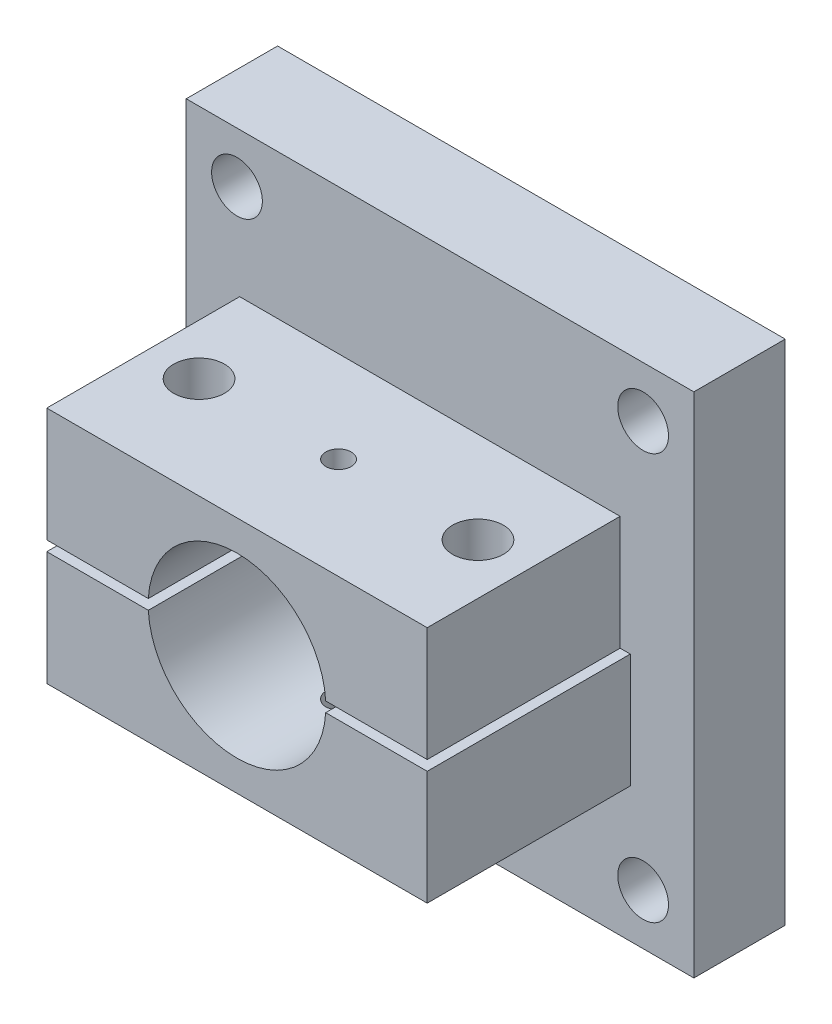
SolidWorks part; units mm, degrees
material "6061-T6 (SS)"
ref_plane "Front Plane" through (0, 0, 0) normal (0, 0, 1) x (1, 0, 0)
ref_plane "Top Plane" through (0, 0, 0) normal (0, 1, 0) x (1, 0, 0)
ref_plane "Right Plane" through (0, 0, 0) normal (1, 0, 0) x (0, 0, -1)
sketch "Sketch1" plane through (0, 0, 0) normal (0, 0, 1) x (1, 0, 0)
  line L0 (0, 31.75) -> (0, -31.75) construction
  line L1 (-31.75, 31.75) -> (31.75, 31.75)
  line L2 (-31.75, 31.75) -> (-31.75, -31.75)
  line L3 (-31.75, -31.75) -> (31.75, -31.75)
  line L4 (31.75, 31.75) -> (31.75, -31.75)
  line L5 (-31.75, 0) -> (31.75, 0) construction
  line L6 (-31.75, 0) -> (-31.75, -0.635)
  line L7 (-31.75, -0.635) -> (0, -0.635) construction
  line L8 (0, -0.635) -> (-11.0943, -0.635) construction
  line L9 (-11.0943, -0.635) -> (-23.7943, -0.635)
  line L10 (-23.7943, -0.635) -> (-23.7943, -14.9225)
  line L11 (-23.7943, -14.9225) -> (23.7943, -14.9225)
  line L12 (11.0943, -0.635) -> (23.7943, -0.635)
  line L13 (23.7943, -0.635) -> (23.7943, -14.9225)
  line L14 (11.0943, 0.635) -> (23.7943, 0.635)
  line L15 (23.7943, 0.635) -> (23.7943, 14.9225)
  line L16 (-23.7943, 14.9225) -> (23.7943, 14.9225)
  line L17 (-23.7943, 0.635) -> (-23.7943, 14.9225)
  line L18 (-11.0943, 0.635) -> (-23.7943, 0.635)
  circle A0 centre (0, 0) radius 11.1125
  circle A1 centre (25.4, 25.4) radius 3.175
  circle A2 centre (-25.4, 25.4) radius 3.175
  circle A3 centre (25.4, -25.4) radius 3.175
  circle A4 centre (-25.4, -25.4) radius 3.175
  point P28 (0, -14.9225)
  dimension "D1" = 22.225
  dimension "D5" = 6.35
  dimension "D3" = 6.35
  dimension "D4" = 6.35
  dimension "D6" = 0.635
  dimension "D7" = 14.9225
  dimension "D8" = 12.7
extrude "Boss-Extrude1" add sketch "Sketch1" along normal blind 6.35 contours L4 L1 L2 L3 A4 A2 A1 A0 L18 L17 L16 L15 L14 L12 L13 L11 L10 L9 A3 | A0 L14 L15 L16 L17 L18 | A0 L9 L10 L11 L13 L12 region at (0, 30.852, 0) region at (0, -11.6094, 0) region at (-17.4443, 1.1319, 0)
extrude "Boss-Extrude2" add sketch "Sketch1<3>" along normal blind 25.4 from surface contours A0 L9 L10 L11 L13 L12 region at (0, -11.6094, 0) starting at face at (11.1125, 0, 6.35)
sketch "Sketch1<3>" plane through (0, 0, 0) normal (0, 0, 1) x (1, 0, 0) same geometry as "Sketch1"
extrude "Boss-Extrude3" add sketch "Sketch1<4>" against normal blind 24.13 from surface separate body contours A0 L14 L15 L16 L17 L18 region at (-17.4443, 1.1319, 0) starting at face at (0, -7.1438, 31.75)
sketch "Sketch1<4>" plane through (0, 0, 0) normal (0, 0, 1) x (1, 0, 0) same geometry as "Sketch1"
sketch "Sketch2" plane through (0, 0, 0) normal (0, 1, 0) x (1, 0, 0)
  line L0 (0, 0) -> (0, -6.35) construction
  line L1 (0, -6.35) -> (0, -31.75) construction
  line L2 (0, -19.05) -> (11.0943, -19.05) construction
  line L5 (11.0943, -19.05) -> (23.7943, -19.05) construction
  line L6 (23.7943, -31.75) -> (23.7943, -6.35) construction
  line L7 (11.0943, -31.75) -> (11.0943, -6.35) construction
  circle A0 centre (17.4443, -19.05) radius 3.175
  circle A1 centre (-17.4443, -19.05) radius 3.175
  circle A2 centre (0, -19.05) radius 1.5875
  dimension "D3" = 6.35
  dimension "D1" = 6.35
  dimension "D4" = 3.175
  dimension "D2" = 25.4
extrude "Cut-Extrude1" cut sketch "Sketch2" against normal through all both and the other way through all
extrude "Boss-Extrude4" add sketch "Sketch1<5>" against normal blind 5.08 contours L4 L1 L2 L3 A4 A2 A1 A0 L18 L17 L16 L15 L14 L12 L13 L11 L10 L9 A3 | A0 L14 L15 L16 L17 L18 | A0 | A0 L9 L10 L11 L13 L12 region at (0, 30.852, 0) region at (0, -11.6094, 0) region at (0, 0, 0) region at (-17.4443, 1.1319, 0)
sketch "Sketch1<5>" plane through (0, 0, 0) normal (0, 0, 1) x (1, 0, 0) same geometry as "Sketch1"
equation "\"Shaft Diameter\"= 7 / 8"
equation "\"Overall Width\"= 2.5"
equation "\"Overall Height\"= 1.25"
equation "\"Bolt Diameter Plate\"= 1 / 4"
equation "\"Bolt Diameter Bracket\"= 1 / 4"
equation "\"D3@Sketch1\"=.25"
equation "\"D2@Sketch1\"=\"Overall Width\""
equation "\"D1@Sketch1\"=\"Shaft Diameter\""
equation "\"Bolt From Edge\"= .25"
equation "\"D4@Sketch1\"=\"Bolt Diameter Plate\""
equation "\"D5@Sketch1\"=\"Bolt Diameter Plate\""
equation "\"Bracket Gap\"= .05"
equation "\"Bracket Plate Thickness\"= .25"
equation "\"D6@Sketch1\"=\"Bracket Gap\"/2"
equation "\"D7@Sketch1\"=\"Shaft Diameter\"/2+.15"
equation "\"D8@Sketch1\"=\"Bolt Diameter Bracket\"*2"
equation "\"D1@Boss-Extrude1\"=\"Bracket Plate Thickness\""
equation "\"D1@Boss-Extrude2\"=\"Overall Height\"-\"Bracket Plate Thickness\""
equation "\"D1@Sketch2\"=\"Bolt Diameter Plate\""
equation "\"D2@Sketch2\"=\"Overall Height\"-\"Bolt Diameter Plate\""
equation "\"D3@Sketch2\"=\"Bolt Diameter Bracket\""
equation "\"D1@Boss-Extrude3\"=\"Overall Height\"-\"Bracket Plate Thickness\"-.05"
equation "\"Pin bolt diameter\"= 1 / 8"
equation "\"D4@Sketch2\"=\"Pin bolt diameter\""
